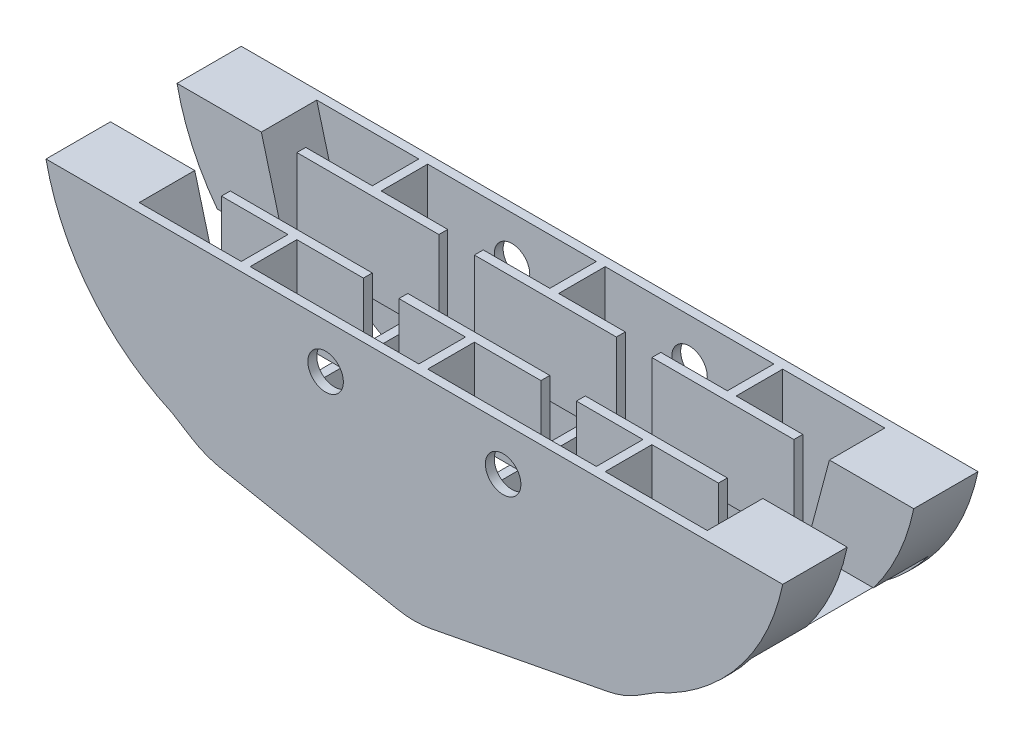
SolidWorks part; units mm, degrees
ref_plane "Front" through (0, 0, 0) normal (0, 0, 1) x (1, 0, 0)
ref_plane "Top" through (0, 0, 0) normal (0, 1, 0) x (1, 0, 0)
ref_plane "Right" through (0, 0, 0) normal (1, 0, 0) x (0, 0, -1)
sketch "Sketch1" plane through (0, 0, 0) normal (0, 0, 1) x (1, 0, 0)
  line L0 (-152.4, 62.23) -> (0, 62.23) construction
  line L1 (-152.4, -62.23) -> (152.4, -62.23) construction
  line L2 (-152.4, -62.23) -> (-152.4, 62.23) construction
  line L3 (-152.4, 62.23) -> (152.4, 62.23) construction
  line L4 (152.4, -62.23) -> (152.4, 62.23) construction
  line L5 (-152.4, -62.23) -> (152.4, 62.23) construction
  line L6 (-152.4, 62.23) -> (152.4, -62.23) construction
  line L7 (-152.4, 62.23) -> (-152.4, -33.02)
  line L8 (-152.4, -33.02) -> (0, -62.23)
  line L9 (0, -62.23) -> (152.4, -32.9764)
  line L10 (152.4, -32.9764) -> (152.4, 62.23)
  line L11 (152.4, 62.23) -> (-152.4, 62.23)
  point P0 (0, 0)
  dimension "D1" = 304.8
  dimension "D2" = 124.46
  dimension "D3" = 95.25
extrude "Boss-Extrude1" add sketch "Sketch1" against normal blind 111.76
ref_plane "Plane1" through (0, 0, -5.08) normal (0, 0, 1) x (1, 0, 0)
sketch "Sketch2" plane through (0, 0, 0) normal (0, 0, 1) x (1, 0, 0)
  line L0 (-152.4, -33.02) -> (-152.4, -13.97) construction
  line L1 (-152.4, 62.23) -> (-152.4, -33.02) construction
  line L2 (152.4, -32.9764) -> (152.4, 62.23) construction
  line L3 (-152.4, -13.97) -> (152.4, -13.97)
  line L4 (-152.4, -13.97) -> (-152.4, 11.43)
  line L5 (-152.4, 11.43) -> (152.4, 11.43)
  line L6 (152.4, -13.97) -> (152.4, 11.43)
  dimension "D1" = 19.05
  dimension "D2" = 25.4
sketch "Sketch5" plane through (0, 0, -5.08) normal (0, 0, 1) x (1, 0, 0)
  line L1 (-152.4, 11.43) -> (152.4, 11.43)
  line L2 (-152.4, 11.43) -> (-152.4, -13.97)
  line L3 (-152.4, -13.97) -> (152.4, -13.97)
  line L4 (152.4, 11.43) -> (152.4, -13.97)
  dimension "D1" = 19.05
  dimension "D2" = 25.4
extrude "Cut-Extrude3" cut sketch "Sketch5" against normal blind 101.6
sketch "Sketch3" plane through (0, 62.23, 0) normal (0, 1, 0) x (1, 0, 0)
  line L0 (152.4, 111.76) -> (-152.4, 111.76) construction
  line L1 (-2.54, 5.08) -> (-99.06, 5.08)
  line L2 (-2.54, 5.08) -> (-2.54, 106.68)
  line L3 (-2.54, 106.68) -> (-99.06, 106.68)
  line L4 (-99.06, 5.08) -> (-99.06, 106.68)
  line L5 (152.4, 0) -> (-152.4, 0) construction
  line L6 (0, 0) -> (0, 111.76) construction
  line L7 (2.54, 106.68) -> (99.06, 106.68)
  line L8 (99.06, 5.08) -> (99.06, 106.68)
  line L9 (2.54, 5.08) -> (99.06, 5.08)
  line L10 (2.54, 5.08) -> (2.54, 106.68)
  line L11 (-152.4, 111.76) -> (-152.4, 0) construction
  line L12 (-104.14, 106.68) -> (-152.4, 106.68)
  line L13 (-104.14, 106.68) -> (-104.14, 5.08)
  line L14 (-104.14, 5.08) -> (-152.4, 5.08)
  line L15 (-152.4, 106.68) -> (-152.4, 5.08)
  line L16 (104.14, 5.08) -> (152.4, 5.08)
  line L17 (152.4, 106.68) -> (152.4, 5.08)
  line L18 (104.14, 106.68) -> (152.4, 106.68)
  line L19 (104.14, 106.68) -> (104.14, 5.08)
  dimension "D1" = 2.54
  dimension "D2" = 96.52
  dimension "D3" = 5.08
  dimension "D4" = 5.08
  dimension "D5" = 5.08
  dimension "D6" = 5.08
  dimension "D7" = 5.08
extrude "Cut-Extrude4" cut sketch "Sketch3" against normal through all both and the other way through all
sketch "Sketch6" plane through (-104.14, 0, 0) normal (-1, 0, 0) x (0, 0, 1)
  line L0 (-5.08, 11.43) -> (-106.68, 11.43) construction
  line L1 (-74.9821, 11.43) -> (-36.8821, 11.43)
  line L2 (-74.9821, 11.43) -> (-74.9821, 62.23)
  line L3 (-74.9821, 62.23) -> (-36.8821, 62.23)
  line L4 (-36.8821, 11.43) -> (-36.8821, 62.23)
  line L5 (-5.08, 62.23) -> (-106.68, 62.23) construction
  dimension "D1" = 38.1
extrude "Cut-Extrude5" cut sketch "Sketch6" against normal up to surface (208.28 mm away) up to face at (104.14, 36.83, -55.88)
ref_plane "Plane2" through (0, 0, -36.8821) normal (0, 0, -1) x (-1, 0, 0)
sketch "Sketch7" plane through (0, 0, -36.8821) normal (0, 0, -1) x (-1, 0, 0)
  line L1 (-40.64, 62.23) -> (40.64, 62.23)
  line L2 (-40.64, 62.23) -> (-40.64, 11.43)
  line L3 (-40.64, 11.43) -> (40.64, 11.43)
  line L4 (40.64, 62.23) -> (40.64, 11.43)
  line L5 (60.96, 62.23) -> (142.24, 62.23)
  line L6 (60.96, 62.23) -> (60.96, 11.43)
  line L7 (60.96, 11.43) -> (142.24, 11.43)
  line L8 (142.24, 62.23) -> (142.24, 11.43)
  line L9 (-142.24, 62.23) -> (-60.96, 62.23)
  line L10 (-142.24, 62.23) -> (-142.24, 11.43)
  line L11 (-142.24, 11.43) -> (-60.96, 11.43)
  line L12 (-60.96, 62.23) -> (-60.96, 11.43)
  dimension "D1" = 38.1
  dimension "D2" = 38.1
  dimension "D3" = 38.1
  dimension "D4" = 38.1
  dimension "D5" = 38.1
  dimension "D6" = 38.1
extrude "Boss-Extrude2" add sketch "Sketch7" against normal blind 5.08
ref_plane "Plane3" through (0, 0, -55.9321) normal (0, 0, -1) x (-1, 0, 0)
mirror "Mirror1" about plane through (0, 0, -55.9321) normal (0, 0, -1) of "Boss-Extrude2"
sketch "Sketch8" plane through (0, 0, 0) normal (0, 0, 1) x (1, 0, 0)
  line L0 (152.4, 62.23) -> (-152.4, 62.23) construction
  circle A0 centre (50.8, 36.83) radius 10.16
  dimension "D1" = 20.32
  dimension "D2" = 25.4
  dimension "D3" = 50.8
extrude "Cut-Extrude6" cut sketch "Sketch8" against normal up to surface (111.76 mm away) up to face at (0, -0.7533, -111.76)
mirror "Mirror2" about plane through (0, 0, 0) normal (1, 0, 0) of "Cut-Extrude6"
sketch "Sketch9" plane through (-152.4, 0, 0) normal (-1, 0, 0) x (0, 0, 1)
  line L1 (-111.76, 62.23) -> (-106.68, 62.23)
  line L2 (-111.76, 62.23) -> (-111.76, -33.02)
  line L3 (-111.76, -33.02) -> (-106.68, -33.02)
  line L4 (-106.68, 62.23) -> (-106.68, -33.02)
  line L5 (-5.08, -33.02) -> (0, -33.02)
  line L6 (-5.08, -33.02) -> (-5.08, 62.23)
  line L7 (-5.08, 62.23) -> (0, 62.23)
  line L8 (0, -33.02) -> (0, 62.23)
extrude "Boss-Extrude3" add sketch "Sketch9" along normal blind 10.16
sketch "Sketch10" plane through (152.4, 0, 0) normal (1, 0, 0) x (0, 0, -1)
  line L1 (0, 62.23) -> (5.08, 62.23)
  line L2 (0, 62.23) -> (0, -32.9764)
  line L3 (0, -32.9764) -> (5.08, -32.9764)
  line L4 (5.08, 62.23) -> (5.08, -32.9764)
  line L5 (106.68, -32.9764) -> (111.76, -32.9764)
  line L6 (106.68, -32.9764) -> (106.68, 62.23)
  line L7 (106.68, 62.23) -> (111.76, 62.23)
  line L8 (111.76, -32.9764) -> (111.76, 62.23)
extrude "Boss-Extrude4" add sketch "Sketch10" along normal blind 10.16
sketch "Sketch11" plane through (0, 0, 0) normal (0, 0, 1) x (1, 0, 0)
  line L0 (-162.56, -12.7) -> (-119.6963, -39.2882)
  line L1 (-162.56, -33.02) -> (-162.56, 62.23) construction
  line L2 (-152.4, -33.02) -> (0, -62.23) construction
  line L3 (-119.6963, -39.2882) -> (-152.4, -33.02)
  line L4 (-152.4, -33.02) -> (-162.56, -33.02)
  line L5 (-162.56, -33.02) -> (-162.56, -12.7)
  line L6 (0, -50) -> (0, 50) construction
  line L7 (152.4, -33.02) -> (162.56, -33.02)
  line L8 (119.6963, -39.2882) -> (152.4, -33.02)
  line L9 (162.56, -12.7) -> (119.6963, -39.2882)
  line L10 (162.56, -33.02) -> (162.56, -12.7)
  dimension "D1" = 20.32
extrude "Cut-Extrude7" cut sketch "Sketch11" against normal up to surface (111.76 mm away) up to face at (-40.64, 36.83, -111.76)
fillet "Fillet1" radius 50.8 9 edges at (-162.56, -12.7, -2.54) (-162.56, -12.7, -109.22) (-119.6963, -39.2882, -109.22) (-119.6963, -39.2882, -2.54) (162.56, -12.7, -109.22) (162.56, -12.7, -2.54) (119.7762, -39.2387, -109.22) (119.7762, -39.2387, -2.54) (0, -62.23, -55.88)
sketch "Sketch12" plane through (0, 0, 0) normal (0, 0, 1) x (1, 0, 0)
  line L0 (-162.56, 62.23) -> (-210.82, 62.23)
  line L1 (-162.56, 62.23) -> (-138.5378, -27.6009)
  line L2 (0, -50) -> (0, 50) construction
  line L3 (162.56, 62.23) -> (210.82, 62.23)
  line L4 (162.56, 62.23) -> (138.5378, -27.6009)
  arc A0 (-138.5378, -27.6009) -> (-210.82, 62.23) centre (-87.1093, 87.7772) cw
  arc A1 (138.5378, -27.6009) -> (210.82, 62.23) centre (87.1093, 87.7772) ccw
  dimension "D1" = 48.26
extrude "Boss-Extrude5" add sketch "Sketch12" against normal up to surface (111.76 mm away) up to face at (-40.64, 36.83, -111.76)
sketch "Sketch13" plane through (0, 0, 0) normal (1, 0, 0) x (0, 0, -1)
  line L0 (36.8821, 62.23) -> (36.8821, 11.43)
  line L1 (36.8821, 11.43) -> (5.08, 11.43)
  line L2 (5.08, 11.43) -> (5.08, -13.97)
  line L3 (5.08, -13.97) -> (106.68, -13.97)
  line L4 (106.68, -13.97) -> (106.68, 11.43)
  line L5 (106.68, 11.43) -> (74.9821, 11.43)
  line L6 (74.9821, 11.43) -> (74.9821, 62.23)
  line L7 (74.9821, 62.23) -> (36.8821, 62.23)
extrude "Cut-Extrude8" cut sketch "Sketch13" against normal up to surface and the other way up to surface up to face at (-166.2475, -0.5666, -55.88) other way up to face at (166.2475, -0.5666, -55.88)
